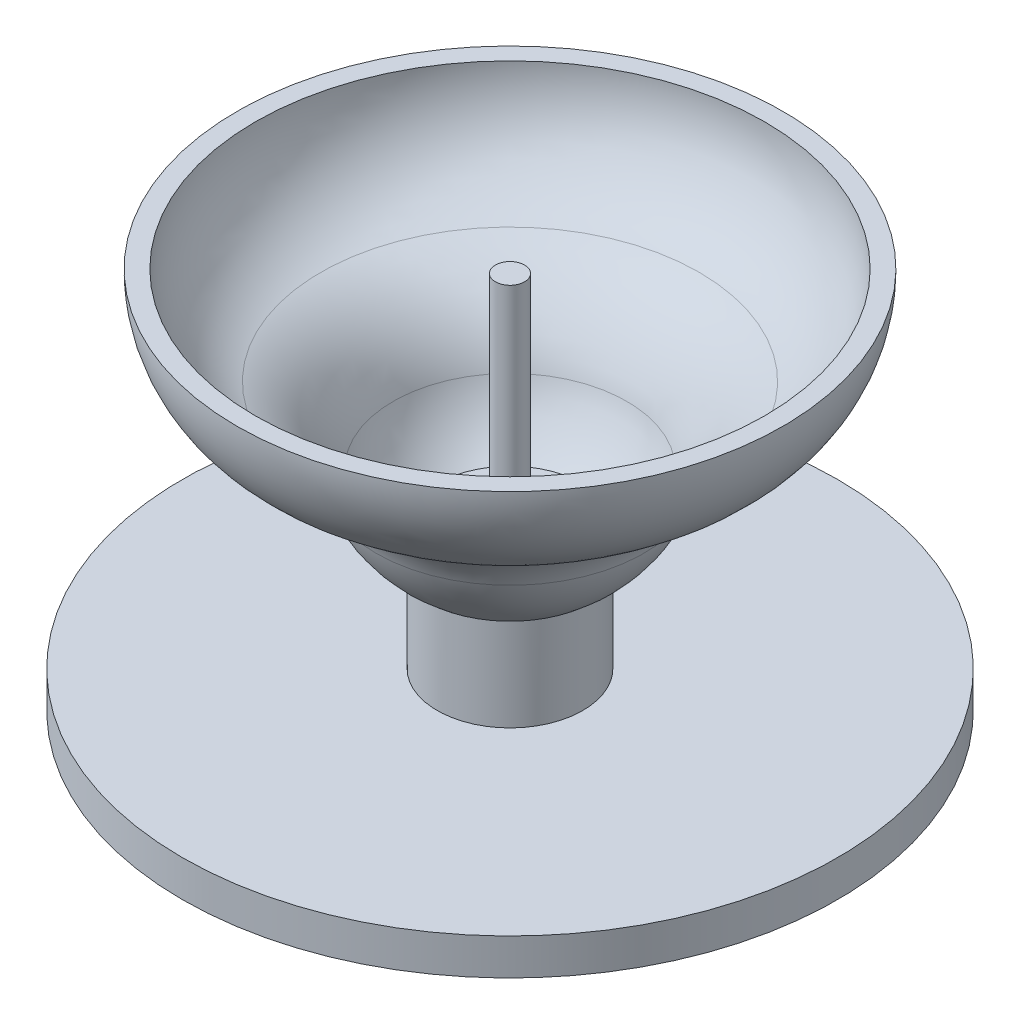
SolidWorks part; units mm, degrees
ref_plane "Plan de face" through (0, 0, 0) normal (0, 0, 1) x (1, 0, 0)
ref_plane "Plan de dessus" through (0, 0, 0) normal (0, 1, 0) x (1, 0, 0)
ref_plane "Plan de droite" through (0, 0, 0) normal (1, 0, 0) x (0, 0, -1)
sketch "Esquisse1" plane through (0, 0, 0) normal (0, 1, 0) x (1, 0, 0)
  circle A0 centre (0, 0) radius 90
  dimension "D1" = 180
extrude "Boss.-Extru.1" add sketch "Esquisse1" along normal blind 10
sketch "Esquisse2" plane through (0, 10, 0) normal (0, 1, 0) x (1, 0, 0)
  circle A0 centre (0, 0) radius 20
  dimension "D1" = 40
extrude "Boss.-Extru.2" add sketch "Esquisse2" along normal blind 93
sketch "Esquisse3" plane through (0, 0, 0) normal (1, 0, 0) x (0, 0, -1)
  line L0 (0, -5.4484) -> (0, 103) construction
  line L2 (-74.9708, 105.0943) -> (-69.9708, 105.0943)
  line L3 (20, 103) -> (-20, 103) construction
  line L4 (0, 103) -> (0, 30)
  line L5 (42.83, 30) -> (-42.83, 30) construction
  line L6 (-74.9708, 105.0943) -> (-74.9708, 140.4054) construction
  line L7 (-69.9708, 105.0943) -> (-69.9708, 119.2286) construction
  line L8 (0, 35) -> (14.583, 35) construction
  line L9 (20, 10) -> (-20, 10) construction
  arc A0 (-74.9708, 105.0943) -> (-53.8936, 73.6441) centre (-40.968, 105.0943) ccw
  arc A1 (-53.8936, 73.6441) -> (-36.8047, 55.814) centre (-65.4918, 45.4237) cw
  arc A2 (-36.8047, 55.814) -> (0, 30) centre (0, 69.1445) ccw
  arc A3 (-69.9708, 105.0943) -> (-51.993, 78.2687) centre (-40.968, 105.0943) ccw
  arc A4 (-51.993, 78.2687) -> (-32.1036, 57.5167) centre (-65.4918, 45.4237) cw
  arc A5 (-32.1036, 57.5167) -> (0, 35) centre (0, 69.1445) ccw
  point P17 (0, 30)
  dimension "D1" = 75
  dimension "D2" = 5
  dimension "D3" = 20
sketch "Esquisse4" plane through (0, 0, 0) normal (0, -1, 0) x (1, 0, 0)
  circle A0 centre (0, 0) radius 36
  circle A1 centre (0, 0) radius 39
  circle A2 centre (0, 0) radius 54
  circle A3 centre (0, 0) radius 57
  circle A4 centre (0, 0) radius 72
  circle A5 centre (0, 0) radius 75
  circle A6 centre (0, 0) radius 90 construction
  dimension "D1" = 3
  dimension "D2" = 3
  dimension "D3" = 3
  dimension "D4" = 15
  dimension "D5" = 15
  dimension "D6" = 15
extrude "Enlèv. mat.-Extru.1" cut sketch "Esquisse4" against normal blind 1 draft 30 contours A5 A4 | A3 A2 | A1 A0 region at (-37.8969, 0, 0) region at (-55.3878, 0, 0) region at (-72.8787, 0, 0)
revolve "Révolution2" add sketch "Esquisse3" angle 360 about L4 region at (0, 63.8067, 41.0309)
sketch "Esquisse5" plane through (0, 103, 0) normal (0, 1, 0) x (1, 0, 0)
  circle A0 centre (0, 0) radius 20
extrude "Enlèv. mat.-Extru.2" cut sketch "Esquisse5" against normal blind 59
sketch "Esquisse6" plane through (0, 44, 0) normal (0, 1, 0) x (1, 0, 0)
  circle A0 centre (0, 0) radius 4
  dimension "D1" = 8
extrude "Boss.-Extru.3" add sketch "Esquisse6" along normal blind 60
